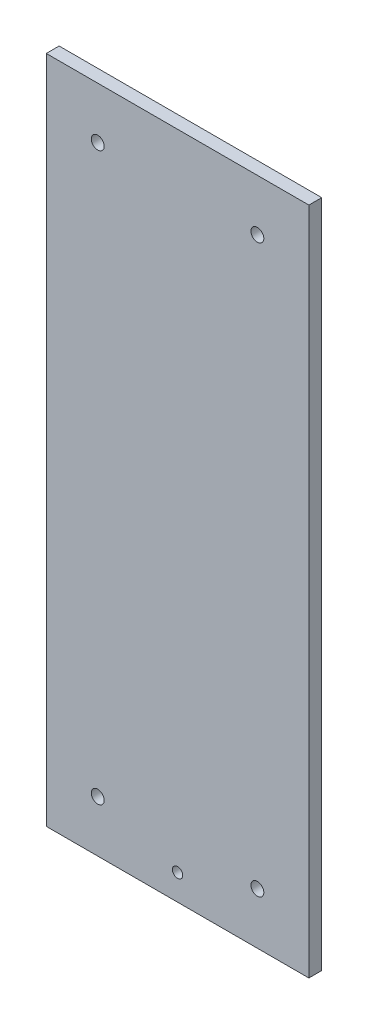
SolidWorks part; units mm, degrees
material "6061 Alloy"
ref_plane "Front" through (0, 0, 0) normal (0, 0, 1) x (1, 0, 0)
ref_plane "Top" through (0, 0, 0) normal (0, 1, 0) x (1, 0, 0)
ref_plane "Right" through (0, 0, 0) normal (1, 0, 0) x (0, 0, -1)
sketch "Sketch1" plane through (0, 0, 0) normal (0, 0, 1) x (1, 0, 0)
  line L1 (0, 0) -> (129.54, 0)
  line L2 (0, 0) -> (0, 330.2)
  line L3 (0, 330.2) -> (129.54, 330.2)
  line L4 (129.54, 0) -> (129.54, 330.2)
  dimension "D1" = 330.2
  dimension "D2" = 129.54
extrude "Main Plate" add sketch "Sketch1" along normal blind 6.35
sketch "Sketch2" plane through (0, 0, 6.35) normal (0, 0, 1) x (1, 0, 0)
  line L0 (0, 330.2) -> (0, 0) construction
  line L1 (129.54, 330.2) -> (0, 330.2) construction
  circle A0 centre (25.4, 304.8) radius 3.175
  dimension "D3" = 6.35
  dimension "D1" = 25.4
  dimension "D2" = 25.4
extrude "Bolt Holes" cut sketch "Sketch2" against normal blind 6.35
pattern_linear "LPattern1" count 2 spacing 78.74 along (1, 0, 0) count 2 spacing 279.4 along (0, -1, 0) of "Bolt Holes"
sketch "Sketch3" plane through (0, 0, 6.35) normal (0, 0, 1) x (1, 0, 0)
  line L0 (0, 330.2) -> (0, 0) construction
  line L1 (0, 0) -> (129.54, 0) construction
  circle A0 centre (64.77, 12.7) radius 2.54
  dimension "D1" = 5.08
  dimension "D2" = 64.77
  dimension "D3" = 12.7
extrude "Wire Hole" cut sketch "Sketch3" against normal blind 6.35
